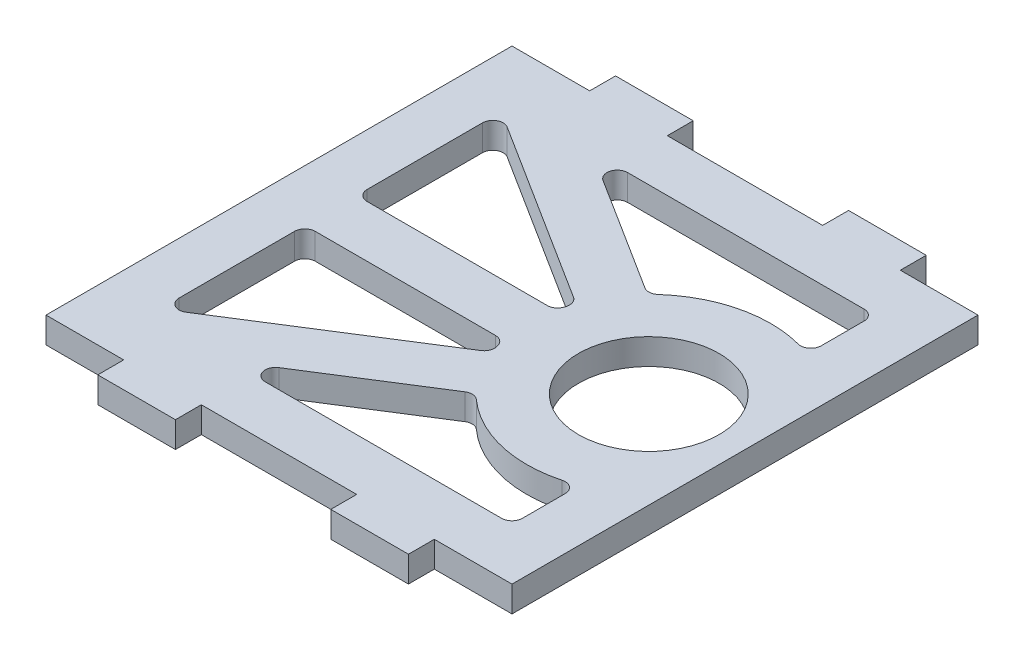
SolidWorks part; units mm, degrees
ref_plane "Front Plane" through (0, 0, 0) normal (0, 0, 1) x (1, 0, 0)
ref_plane "Top Plane" through (0, 0, 0) normal (0, 1, 0) x (1, 0, 0)
ref_plane "Right Plane" through (0, 0, 0) normal (1, 0, 0) x (0, 0, -1)
sketch "Sketch1" plane through (0, 0, 0) normal (0, 1, 0) x (1, 0, 0)
  line L0 (0, 57.15) -> (184.6638, 57.15) construction
  line L1 (0, 0) -> (19.05, 0)
  line L3 (0, 114.3) -> (19.05, 114.3)
  line L4 (114.3, 0) -> (114.3, 114.3)
  line L5 (38.1, 0) -> (76.2, 0)
  line L7 (95.25, 0) -> (95.25, -6.35)
  line L8 (95.25, -6.35) -> (76.2, -6.35)
  line L9 (76.2, 0) -> (76.2, -6.35)
  line L11 (19.05, 0) -> (19.05, -6.35)
  line L12 (19.05, -6.35) -> (38.1, -6.35)
  line L13 (38.1, 0) -> (38.1, -6.35)
  line L14 (95.25, 0) -> (114.3, 0)
  line L15 (38.1, 114.3) -> (38.1, 120.65)
  line L16 (19.05, 120.65) -> (38.1, 120.65)
  line L17 (19.05, 114.3) -> (19.05, 120.65)
  line L18 (76.2, 114.3) -> (76.2, 120.65)
  line L19 (95.25, 120.65) -> (76.2, 120.65)
  line L20 (95.25, 114.3) -> (95.25, 120.65)
  line L21 (38.1, 114.3) -> (76.2, 114.3)
  line L23 (95.25, 114.3) -> (114.3, 114.3)
  line L32 (0, 0) -> (0, 114.3)
  point P23 (39.9281, -6.35)
  point P24 (0, 0)
  dimension "D1" = 114.3
  dimension "D2" = 114.3
  dimension "D3" = 19.05
  dimension "D4" = 19.05
  dimension "D5" = 19.05
  dimension "D6" = 19.05
  dimension "D7" = 6.35
extrude "Boss-Extrude1" add sketch "Sketch1" against normal blind 6.35
sketch "Sketch2" plane through (0, 0, 0) normal (0, 1, 0) x (1, 0, 0)
  line L0 (114.3, 57.15) -> (55.59, 57.15) construction
  line L1 (114.3, 0) -> (114.3, 114.3) construction
  line L2 (107.95, 57.15) -> (107.95, 78.6846) construction
  circle A0 centre (90.7, 57.15) radius 17.25
  point P8 (0, 0)
  dimension "D1" = 34.5001
  dimension "D2" = 6.35
extrude "Cut-Extrude1" cut sketch "Sketch2" against normal through all
sketch "Sketch3" plane through (0, 0, 0) normal (0, 1, 0) x (1, 0, 0)
  line L0 (90.7, 57.15) -> (-12.2602, 122.2732) construction
  line L1 (87.3056, 51.7834) -> (-15.6546, 116.9066)
  line L2 (94.0944, 62.5166) -> (-8.8658, 127.6398)
  line L3 (90.7, 57.15) -> (22.3264, 57.15) construction
  line L4 (90.7, 57.15) -> (-12.2602, -7.9732) construction
  line L5 (87.3056, 62.5166) -> (-15.6546, -2.6066)
  line L6 (94.0944, 51.7834) -> (-8.8658, -13.3398)
  line L35 (90.7, 57.15) -> (-12.2602, 57.15) construction
  line L36 (90.7, 50.8) -> (-12.2602, 50.8)
  line L37 (90.7, 63.5) -> (-12.2602, 63.5)
  line L63 (12.7, 12.7) -> (101.6, 12.7)
  line L64 (101.6, 12.7) -> (101.6, 101.6)
  line L65 (101.6, 101.6) -> (12.7, 101.6)
  line L66 (12.7, 101.6) -> (12.7, 12.7)
  line L67 (12.7, 12.7) -> (101.6, 12.7)
  line L68 (101.6, 12.7) -> (101.6, 101.6)
  line L69 (101.6, 101.6) -> (12.7, 101.6)
  line L70 (12.7, 101.6) -> (12.7, 12.7)
  arc A0 (87.3056, 51.7834) -> (94.0944, 62.5166) centre (90.7, 57.15) ccw
  arc A1 (-8.8658, 127.6398) -> (-15.6546, 116.9066) centre (-12.2602, 122.2732) ccw
  arc A3 (87.3056, 62.5166) -> (94.0944, 51.7834) centre (90.7, 57.15) cw
  circle A4 centre (90.7, 57.15) radius 29.95
  circle A5 centre (90.7, 57.15) radius 29.95
  arc A6 (-8.8658, -13.3398) -> (-15.6546, -2.6066) centre (-12.2602, -7.9732) cw
  arc A7 (90.7, 50.8) -> (90.7, 63.5) centre (90.7, 57.15) ccw
  arc A8 (-12.2602, 63.5) -> (-12.2602, 50.8) centre (-12.2602, 57.15) ccw
  point P2 (39.2199, 89.7116)
  point P8 (39.2199, 24.5884)
  point P19 (39.2199, 57.15)
  dimension "D2" = 6.35
  dimension "D1" = 12.7
  dimension "D3" = 12.7
extrude "Cut-Extrude2" cut sketch "Sketch3" against normal through all contours A5 L68 L69 L2 | A5 L1 L70 L37 | A5 L36 L70 L5 | A5 L6 L67 L68 region at (30.9036, 0, -75.4809) region at (30.9036, 0, -38.8191) region at (72.1425, 0, -20.8641) region at (72.1425, 0, -93.4359)
fillet "Fillet1" radius 2.54 16 edges at (61.4308, -3.175, -63.5) (12.7, -3.175, -63.5) (62.5692, -3.175, -67.4293) (101.6, -3.175, -29.2539) (101.6, -3.175, -12.7) (32.3033, -3.175, -12.7) (69.3581, -3.175, -36.1375) (69.3581, -3.175, -78.1625) (32.3033, -3.175, -101.6) (101.6, -3.175, -101.6) (101.6, -3.175, -85.0461) (62.5692, -3.175, -46.8707) (12.7, -3.175, -15.328) (12.7, -3.175, -50.8) (61.4308, -3.175, -50.8) (12.7, -3.175, -98.972)
